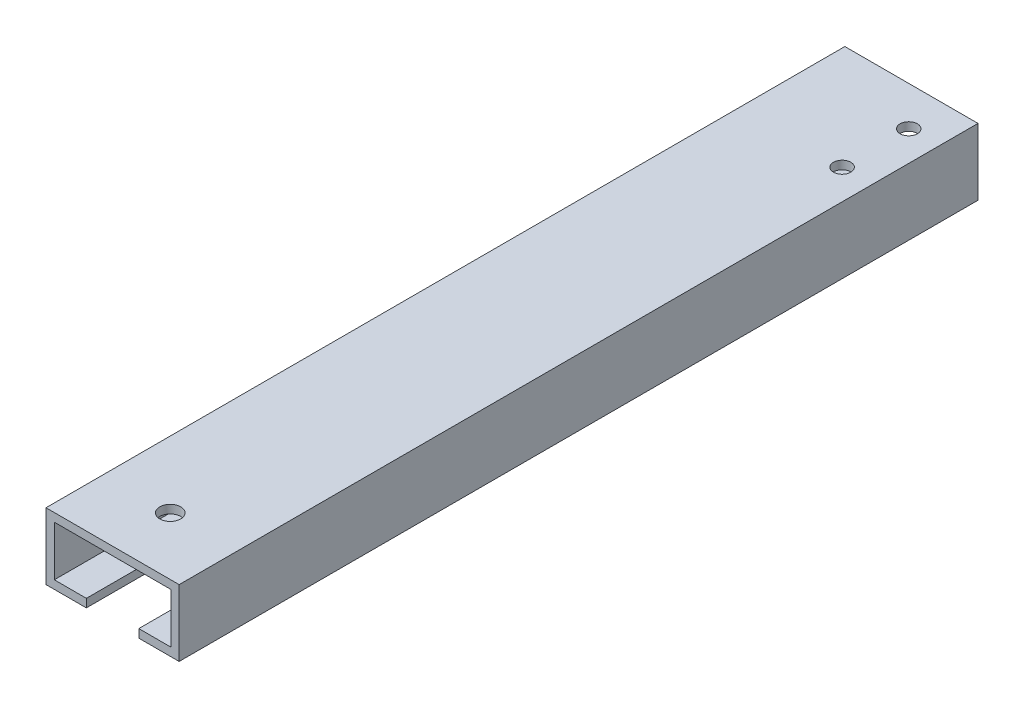
SolidWorks part; units mm, degrees
material "6061 Alloy"
ref_plane "Front Plane" through (0, 0, 0) normal (0, 0, 1) x (1, 0, 0)
ref_plane "Top Plane" through (0, 0, 0) normal (0, 1, 0) x (1, 0, 0)
ref_plane "Right Plane" through (0, 0, 0) normal (1, 0, 0) x (0, 0, -1)
sketch "Sketch1" plane through (0, 0, 0) normal (0, 0, 1) x (1, 0, 0)
  line L0 (-11.1125, 4.7625) -> (11.1125, 4.7625)
  line L2 (-12.7, 6.35) -> (12.7, 6.35)
  line L3 (-12.7, 6.35) -> (-12.7, -6.35)
  line L4 (-12.7, -6.35) -> (12.7, -6.35)
  line L5 (12.7, 6.35) -> (12.7, -6.35)
  line L10 (11.1125, 4.7625) -> (11.1125, -4.7625)
  line L11 (-11.1125, -4.7625) -> (11.1125, -4.7625)
  line L12 (-11.1125, 4.7625) -> (-11.1125, -4.7625)
  point P12 (0, 6.35)
  point P14 (12.7, 0)
  dimension "Wall Thickness" = 1.5875
  dimension "Outside Width" = 25.4
  dimension "Outside Height" = 12.7
  dimension "Inside Height" = 9.525
  dimension "Inside Width" = 22.225
sketch "Sketch2" plane through (0, 0, 0) normal (1, 0, 0) x (0, 0, -1)
  line L0 (304.8, 0) -> (-304.8, 0)
  point P4 (0, 0)
  point P7 (-304.8, 0)
  point P10 (304.8, 0)
  dimension "Length" = 609.6
sketch "Sketch3" plane through (0, 0, 0) normal (0, 0, 1) x (1, 0, 0)
  line L21 (12.7, 6.35) -> (-12.7, 6.35)
  line L22 (12.7, -6.35) -> (12.7, 6.35)
  line L23 (-12.7, -6.35) -> (12.7, -6.35)
  line L24 (-12.7, 6.35) -> (-12.7, -6.35)
  line L25 (12.7, 6.35) -> (-12.7, 6.35)
  line L26 (12.7, -6.35) -> (12.7, 6.35)
  line L27 (-12.7, -6.35) -> (12.7, -6.35)
  line L28 (-12.7, 6.35) -> (-12.7, -6.35)
  line L29 (11.1125, 4.7625) -> (-11.1125, 4.7625)
  line L30 (11.1125, -4.7625) -> (11.1125, 4.7625)
  line L31 (-11.1125, -4.7625) -> (11.1125, -4.7625)
  line L32 (-11.1125, 4.7625) -> (-11.1125, -4.7625)
  line L33 (11.1125, 4.7625) -> (-11.1125, 4.7625)
  line L34 (11.1125, -4.7625) -> (11.1125, 4.7625)
  line L35 (-11.1125, -4.7625) -> (11.1125, -4.7625)
  line L36 (-11.1125, 4.7625) -> (-11.1125, -4.7625)
  dimension "D1" = 0
  dimension "D2" = 0
extrude "Boss-Extrude1" add sketch "Sketch3" along normal blind 152.4
sketch "Drawing Reference" plane through (0, 0, 0) normal (1, 0, 0) x (0, 0, -1)
  line L0 (-304.8, 0) -> (304.8, 0) construction
  line L1 (-76.2, -6.35) -> (-76.2, 6.35) construction
  line L2 (-152.4, -6.35) -> (0, -6.35) construction
  line L5 (-152.4, 6.35) -> (0, 6.35) construction
  point P7 (-286.512, 0)
  point P8 (134.112, 0)
  dimension "D1" = 18.288
sketch "Sketch4" plane through (0, 6.35, 0) normal (0, 1, 0) x (1, 0, 0)
  line L0 (-12.7, -152.4) -> (-12.7, 0) construction
  line L1 (12.7, -152.4) -> (-12.7, -152.4) construction
  circle A0 centre (0, -141.4) radius 2
  dimension "D1" = 4
  dimension "D2" = 11
  dimension "D3" = 12.7
extrude "Cut-Extrude1" cut sketch "Sketch4" against normal up to surface (1.5875 mm away) up to face at (0, 4.7625, 76.2)
sketch "Sketch5" plane through (0, -6.35, 0) normal (0, -1, 0) x (1, 0, 0)
  circle A1 centre (-8, 141.4) radius 1.5004
  circle A2 centre (0, 149.4) radius 1.5004
  circle A3 centre (8, 141.4) radius 1.5004
  point P12 (0, 141.4)
extrude "Cut-Extrude2" cut sketch "Sketch5" against normal up to surface (1.5875 mm away) up to face at (0, -4.7625, 76.2)
sketch "Sketch6" plane through (0, -6.35, 0) normal (0, -1, 0) x (1, 0, 0)
  line L0 (-5, 152.4) -> (-5, 136.4)
  line L1 (-12.7, 152.4) -> (12.7, 152.4) construction
  line L2 (-5, 136.4) -> (5, 136.4)
  line L3 (5, 136.4) -> (5, 152.4)
  line L4 (-8, 141.4) -> (8, 141.4) construction
  line L5 (0, 149.4) -> (0, 127.1732) construction
  circle A0 centre (-8, 141.4) radius 1.5004 construction
  circle A1 centre (8, 141.4) radius 1.5004 construction
  circle A3 centre (0, 141.4) radius 5 construction
  point P18 (0, 141.4)
  dimension "D1" = 10
extrude "Cut-Extrude3" cut sketch "Sketch6" against normal blind 2.54 and the other way through all
ref_plane "Plane1" through (0, -6.35, 0) normal (0, -1, 0) x (-1, 0, 0)
sketch "Sketch7" plane through (0, -6.35, 0) normal (0, -1, 0) x (-1, 0, 0)
  line L0 (-12.7, -152.4) -> (-12.7, 0) construction
  line L1 (12.7, 0) -> (-12.7, 0) construction
  point P0 (-6.985, -20.2)
  point P1 (-6.985, -7.5)
  dimension "D1" = 12.7
  dimension "D2" = 5.715
  dimension "D3" = 20.2
  dimension "D4" = 7.5
hole_wizard "M4x0.7 Tapped Hole1" positions "Sketch8" profile "Sketch9" tap size "M4x0.7" standard "ANSI Metric" end condition through all
sketch "Sketch8" plane through (0, -6.35, 0) normal (0, -1, 0) x (-1, 0, 0)
  point P0 (-6.985, -20.2)
  point P3 (-6.985, -7.5)
sketch "Sketch9" plane through (6.985, -6.35, 20.2) normal (1, 0, 0) x (0, 0, -1)
  line L0 (0, 0) -> (0, 12.7)
  line L1 (0, 12.7) -> (1.65, 12.7)
  line L2 (1.65, 12.7) -> (1.65, 0)
  line L5 (1.65, 0) -> (0, 0)
  line L11 (0, -6.35) -> (0, 107.95) construction
  dimension "Thru Tap Drill Dia." = 3.3
  dimension "Thru Tap Drill Depth" = 12.7
equation "\"D1@Drawing Reference\"=\"Outside Width@Sketch1\" * 0.72"
